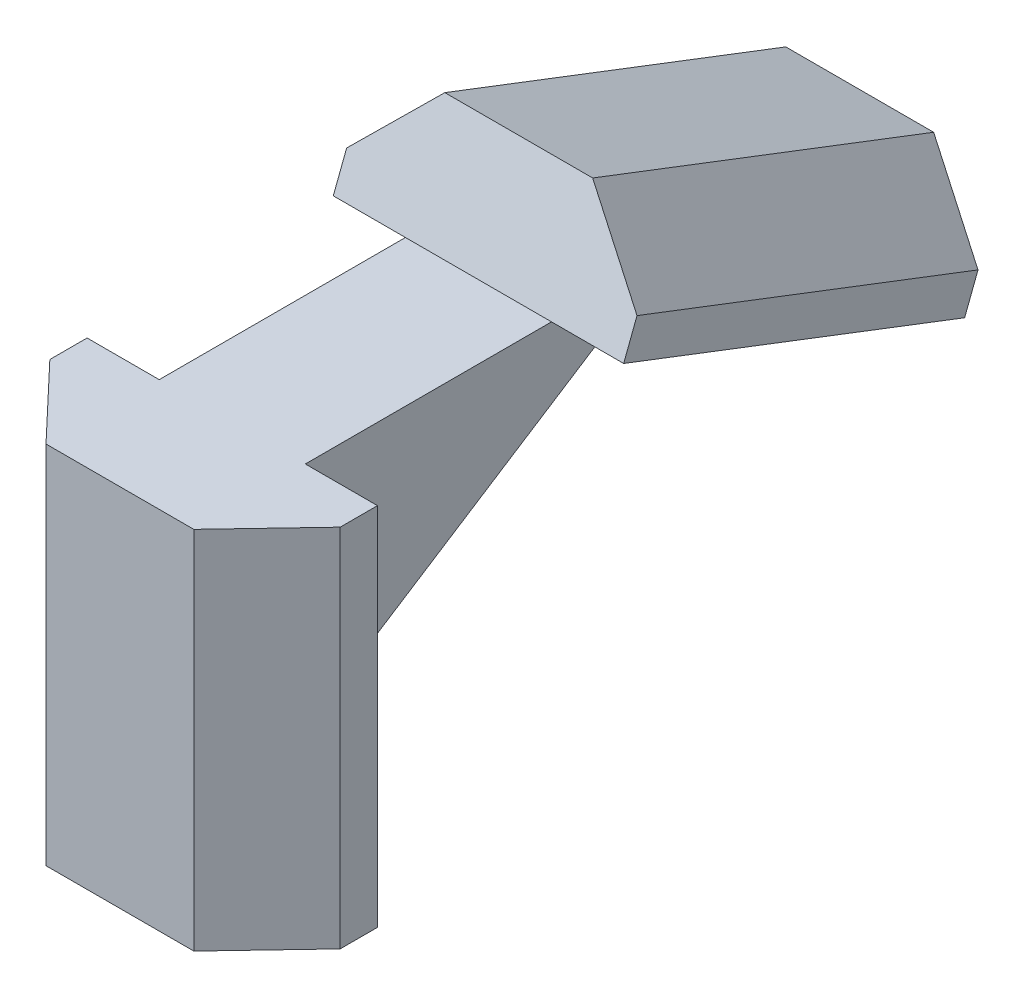
SolidWorks part; units mm, degrees
ref_plane "Front Plane" through (0, 0, 0) normal (0, 0, 1) x (1, 0, 0)
ref_plane "Top Plane" through (0, 0, 0) normal (0, 1, 0) x (1, 0, 0)
ref_plane "Right Plane" through (0, 0, 0) normal (1, 0, 0) x (0, 0, -1)
sketch "Sketch1" plane through (0, 0, 0) normal (0, 1, 0) x (1, 0, 0)
  line L4 (0, 0) -> (0, 4.5954) construction
  line B0 (7.95, 0) -> (7.95, -2.04)
  line B1 (4.048, -6.1524) -> (-4.048, -6.1524)
  line B2 (-7.95, -2.04) -> (-7.95, 0)
  line B3 (-7.95, 0) -> (7.95, 0)
  line B4 (7.95, -2.04) -> (4.048, -6.1524)
  line B5 (-4.048, -6.1524) -> (-7.95, -2.04)
  line B6 (4.05, 0) -> (-4.05, 0) construction
sketch_block_instance "Extrusion Profile-2"
sketch_block "Extrusion Profile" parameters "D1"=8.44, "D2"=2.6, "D3"=6, "D4"=16.7, "D6"=5.6686, "D7"=2.0404, "D8"=8.0963, "D9"=15.9, "D5"=2.4157
extrude "Boss-Extrude1" add sketch "Sketch1" against normal blind 20 contours B2 B5 B1 B4 B0 B3
ref_plane "Plane1" through (0, 0, 0) normal (1, 0, 0) x (0, 0, -1)
sketch "Sketch2" plane through (0, 0, 0) normal (1, 0, 0) x (0, 0, -1)
  line L10 (5.1098, 0) -> (23.7814, -7.1674)
  line L12 (5.1098, 0) -> (6.1849, 2.8007)
  line L13 (6.1849, 2.8007) -> (24.8565, -4.3666)
  line L14 (24.8565, -4.3666) -> (23.7814, -7.1674)
  line L15 (0, -20) -> (0, 0) construction
  point P2 (0, 0)
  point P3 (0, 0)
  point P4 (0, 0)
  point P5 (23.7814, -7.1674)
  point P6 (0, 0)
  point P10 (0, 0)
  point P15 (0, 0)
  dimension "D1" = 69
  dimension "D2" = 3
  dimension "D3" = 20
  dimension "D4" = 5.1098
sketch "Sketch4" plane through (0, 0, 0) normal (1, 0, 0) x (0, 0, -1)
  line L0 (0, 0) -> (13.4811, 0)
  line L1 (6.1849, 2.8007) -> (24.8565, -4.3666) construction
  line L2 (13.4811, 0) -> (17.2781, -1.4575)
  line L3 (17.2781, -1.4575) -> (0, -12.5397)
  line L6 (0, 0) -> (0, -12.5397)
  point P6 (0, 0)
  point P9 (0, -12.5397)
  dimension "D1" = 10.5551
  dimension "D2" = 20.5267
extrude "Boss-Extrude3" add sketch "Sketch4" along normal mid plane 8
sketch "Sketch11" plane through (0, 4.5103, -1.7313) normal (0, 0.9336, -0.3584) x (1, 0, 0)
  line L0 (-4, 16.6528) -> (-4, 12.5857)
  line L1 (-4, 12.5857) -> (4, 12.5857)
  line L2 (4, 12.5857) -> (4, 16.6528)
  line L3 (4, 16.6528) -> (-4, 16.6528)
extrude "Boss-Extrude8" add sketch "Sketch11" along normal blind 1
sketch "Sketch10" plane through (0, -4.5103, -11.7497) normal (0, 0.3584, 0.9336) x (1, 0, 0)
  point P0 (-9.146, 8.4541)
  line B0 (-7.95, 4.8312) -> (-7.95, 6.8712)
  line B1 (-4.048, 10.9836) -> (4.048, 10.9836)
  line B2 (7.95, 6.8712) -> (7.95, 4.8312)
  line B3 (7.95, 4.8312) -> (-7.95, 4.8312)
  line B4 (-7.95, 6.8712) -> (-4.048, 10.9836)
  line B5 (4.048, 10.9836) -> (7.95, 6.8712)
sketch_block_instance "Extrusion Profile-4"
extrude "Boss-Extrude7" add sketch "Sketch10" against normal blind 20
